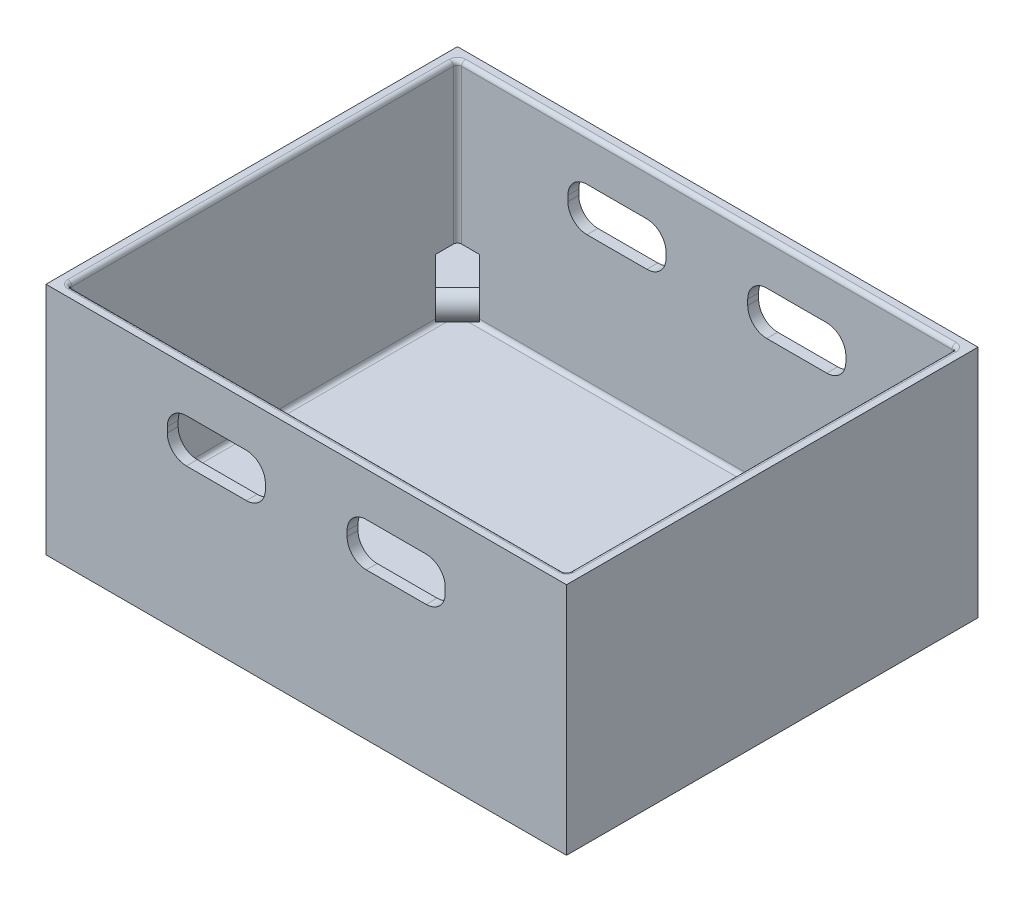
SolidWorks part; units mm, degrees
ref_plane "Front Plane" through (0, 0, 0) normal (0, 0, 1) x (1, 0, 0)
ref_plane "Top Plane" through (0, 0, 0) normal (0, 1, 0) x (1, 0, 0)
ref_plane "Right Plane" through (0, 0, 0) normal (1, 0, 0) x (0, 0, -1)
sketch "Sketch1" plane through (0, 0, 0) normal (0, 1, 0) x (1, 0, 0)
  line L1 (-45.75, 35.75) -> (45.75, 35.75)
  line L2 (-45.75, 35.75) -> (-45.75, -35.75)
  line L3 (-45.75, -35.75) -> (45.75, -35.75)
  line L4 (45.75, 35.75) -> (45.75, -35.75)
  line L5 (-45.75, 35.75) -> (45.75, -35.75) construction
  line L6 (-45.75, -35.75) -> (45.75, 35.75) construction
  point P0 (0, 0)
  dimension "D1" = 91.5
  dimension "D2" = 71.5
extrude "Extrude-Thin1" add sketch "Sketch1" along normal blind 40 thin thin type one direction wall 2
sketch "Sketch2" plane through (0, 0, 0) normal (0, -1, 0) x (1, 0, 0)
  line L1 (-47.75, 37.75) -> (47.75, 37.75)
  line L2 (-47.75, 37.75) -> (-47.75, -37.75)
  line L3 (-47.75, -37.75) -> (47.75, -37.75)
  line L4 (47.75, 37.75) -> (47.75, -37.75)
extrude "Boss-Extrude1" add sketch "Sketch2" along normal blind 3
sketch "Sketch3" plane through (0, 0, 0) normal (0, 1, 0) x (1, 0, 0)
  line L1 (-45.75, 35.75) -> (-33.25, 35.75)
  line L2 (-45.75, 35.75) -> (-45.75, 25.75)
  line L3 (-45.75, 25.75) -> (-33.25, 25.75)
  line L4 (-33.25, 35.75) -> (-33.25, 25.75)
  line L5 (-45.75, -35.75) -> (-33.25, -35.75)
  line L6 (-45.75, -35.75) -> (-45.75, -25.75)
  line L7 (-45.75, -25.75) -> (-33.25, -25.75)
  line L8 (-33.25, -35.75) -> (-33.25, -25.75)
  line L9 (45.75, -35.75) -> (33.25, -35.75)
  line L10 (45.75, -35.75) -> (45.75, -25.75)
  line L11 (45.75, -25.75) -> (33.25, -25.75)
  line L12 (33.25, -35.75) -> (33.25, -25.75)
  line L13 (45.75, 35.75) -> (33.25, 35.75)
  line L14 (45.75, 35.75) -> (45.75, 25.75)
  line L15 (45.75, 25.75) -> (33.25, 25.75)
  line L16 (33.25, 35.75) -> (33.25, 25.75)
  dimension "D1" = 10
  dimension "D2" = 12.5
  dimension "D3" = 12.5
  dimension "D4" = 10
extrude "Boss-Extrude2" [suppressed] add sketch "Sketch3" along normal blind 3 from offset 11
sketch "Sketch4" plane through (0, 0, 37.75) normal (0, 0, 1) x (1, 0, 0)
  line L0 (-47.75, 40) -> (47.75, 40) construction
  line L1 (-22, 32) -> (-11, 32)
  line L2 (-25.5, 28.5) -> (-25.5, 27.5)
  line L3 (-22, 24) -> (-11, 24)
  line L4 (-7.5, 28.5) -> (-7.5, 27.5)
  line L5 (11, 32) -> (22, 32)
  line L6 (7.5, 28.5) -> (7.5, 27.5)
  line L7 (11, 24) -> (22, 24)
  line L8 (25.5, 28.5) -> (25.5, 27.5)
  line L9 (-7.5, 24) -> (7.5, 24) construction
  arc A0 (22, 24) -> (25.5, 27.5) centre (22, 27.5) ccw
  arc A1 (22, 32) -> (25.5, 28.5) centre (22, 28.5) cw
  arc A2 (11, 32) -> (7.5, 28.5) centre (11, 28.5) ccw
  arc A3 (7.5, 27.5) -> (11, 24) centre (11, 27.5) ccw
  arc A4 (-11, 32) -> (-7.5, 28.5) centre (-11, 28.5) cw
  arc A5 (-11, 24) -> (-7.5, 27.5) centre (-11, 27.5) ccw
  arc A6 (-22, 32) -> (-25.5, 28.5) centre (-22, 28.5) ccw
  arc A7 (-25.5, 27.5) -> (-22, 24) centre (-22, 27.5) ccw
  point P11 (0, 24)
  point P28 (-25.5, 32)
  point P31 (-25.5, 24)
  dimension "D5" = 3.5
  dimension "D1" = 18
  dimension "D2" = 8
  dimension "D3" = 15
  dimension "D4" = 8
extrude "Cut-Extrude1" cut sketch "Sketch4" against normal through all
fillet "Fillet1" [suppressed] radius 0.75
fillet "Fillet2" [suppressed] radius 1
sketch "Sketch7" plane through (0, 0, 0) normal (0, 1, 0) x (1, 0, 0)
  line L2 (-45.75, 35.75) -> (-45.75, -35.75) construction
  line L3 (45.75, 35.75) -> (-45.75, 35.75) construction
  line L4 (45.75, 35.75) -> (-45.75, 35.75)
  line L5 (-45.75, 35.75) -> (-45.75, -35.75)
  line L10 (-45.75, 31.75) -> (-41.75, 35.75) construction
  line L11 (-45.75, 31.75) -> (-38.6789, 24.6789)
  line L12 (-38.6789, 24.6789) -> (-34.6789, 28.6789)
  line L13 (-34.6789, 28.6789) -> (-41.75, 35.75)
  line M13 (-45.75, 35.75) -> (-45.75, -35.75)
  dimension "D1" = 45
  dimension "D2" = 4
  dimension "D3" = 10
extrude "Boss-Extrude3" add sketch "Sketch7" against normal blind 9 from offset 11 contours L10 L11 L12 L13 | L10 L4 M13 region at (-44.4167, 0, -34.4167) region at (-40.2145, 0, -30.2145)
sketch "Sketch8" plane through (-7, 0, 7) normal (-0.7071, 0, 0.7071) x (0.7071, 0, 0.7071)
  line L0 (-46.8008, 5.9325) -> (-53.5508, 2)
  line L4 (-44.8008, 11) -> (-54.8008, 11)
  line L5 (-54.8008, 11) -> (-54.8008, 2)
  line L6 (-54.8008, 2) -> (-44.8008, 2)
  line L7 (-44.8008, 2) -> (-44.8008, 11)
  line L8 (-44.8008, 11) -> (-54.8008, 11)
  line L10 (-54.8008, 2) -> (-44.8008, 2)
  line L11 (-44.8008, 2) -> (-44.8008, 11)
  line L14 (-54.8008, 11) -> (-54.8008, 2)
  arc A0 (-47.3008, 11) -> (-46.8008, 5.9325) centre (-48.2103, 8.3518) cw
  line M6 (-44.8008, 11) -> (-54.8008, 11)
  line M8 (-54.8008, 2) -> (-44.8008, 2)
  line M9 (-44.8008, 2) -> (-44.8008, 11)
  dimension "D3" = 2.8
  dimension "D2" = 2.5
  dimension "D5" = 2
  dimension "D1" = 0
extrude "Cut-Extrude2" cut sketch "Sketch8" against normal up to next contours A0 L0 M6 M8 M9 region at (-40.4816, 4.5822, -26.4816)
mirror "Mirror1" about plane through (0, 0, 0) normal (0, 0, 1) of "Cut-Extrude2", "Boss-Extrude3"
mirror "Mirror2" about plane through (0, 0, 0) normal (1, 0, 0) of "Mirror1", "Cut-Extrude2", "Boss-Extrude3"
fillet "Fillet3" radius 0.75 8 edges at (-45.75, 0, 0) (0, 0, 35.75) (45.75, 0, 0) (0, 0, -35.75) (45.75, 25.5, 35.75) (45.75, 25.5, -35.75) (-45.75, 25.5, -35.75) (-45.75, 25.5, 35.75)
fillet "Fillet4" radius 0.75 8 edges at (-45.5303, 40, -35.5303) (0, 40, -35.75) (45.5303, 40, -35.5303) (45.75, 40, 0) (45.5303, 40, 35.5303) (0, 40, 35.75) (-45.5303, 40, 35.5303) (-45.75, 40, 0)
